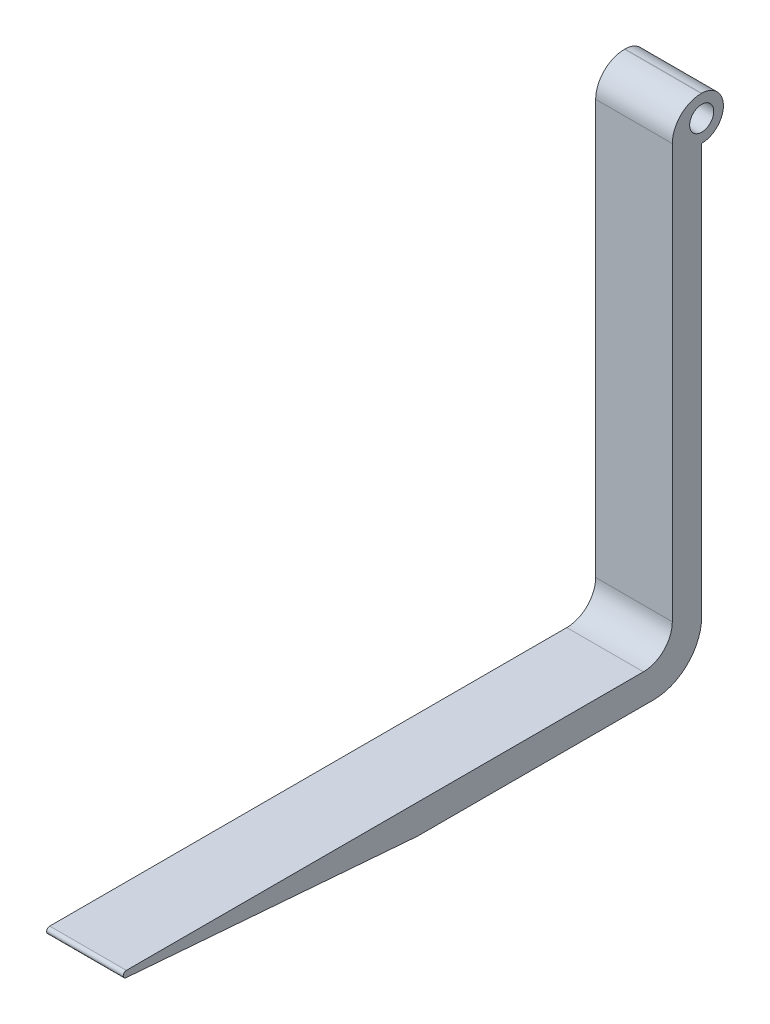
SolidWorks part; units mm, degrees
ref_plane "Front Plane" through (0, 0, 0) normal (0, 0, 1) x (1, 0, 0)
ref_plane "Top Plane" through (0, 0, 0) normal (0, 1, 0) x (1, 0, 0)
ref_plane "Right Plane" through (0, 0, 0) normal (1, 0, 0) x (0, 0, -1)
sketch "Sketch1" plane through (0, 0, 0) normal (1, 0, 0) x (0, 0, -1)
  line L0 (-622.5, -459) -> (516.5, -459)
  line L1 (516.5, -459) -> (516.5, 430)
  line L2 (577.5, 430) -> (577.5, -520)
  line L3 (577.5, -520) -> (-12.5, -520)
  line L4 (516.5, 430) -> (516.5, 520)
  line L5 (516.5, 430) -> (516.5, -445)
  line L6 (502.5, -459) -> (-622.5, -459)
  line L7 (-622.5, -471.5) -> (-12.5, -520)
  line L8 (-12.5, -520) -> (502.5, -520)
  line L9 (577.5, -445) -> (577.5, 430)
  line L10 (-622.5, -471.5) -> (-622.5, -459)
  line L11 (516.5, 520) -> (577.5, 520)
  arc A0 (577.5, 430) -> (577.5, 520) centre (577.5, 475) ccw
  circle A2 centre (577.5, 475) radius 25
  arc A3 (577.5, 430) -> (577.5, 520) centre (577.5, 475) ccw
extrude "Boss-Extrude1" add sketch "Sketch1" along normal blind 159 contours L2 A0 L11 L4 L1 L0 L10 L7 L3 A2 region at (0, -475.2223, 60)
fillet "Fillet1" radius 60 1 edges at (79.5, 520, -516.5) type face fillet first side face at (79.5, 520, -547) second side face at (79.5, 30.5, -516.5)
fillet "Fillet2" radius 60 1 edges at (79.5, -459, -516.5)
fillet "Fillet3" radius 100 1 edges at (79.5, -520, -577.5) type face fillet first side face at (79.5, -520, -282.5) second side face at (79.5, -45, -577.5)
fillet "Fillet4" 2 edges at (79.5, -459, 622.5) (79.5, -471.5, 622.5) type full round first side face at (79.5, -459, 83) second side face at (79.5, -495.75, 317.5) middle face at (79.5, -465.25, 622.5)
